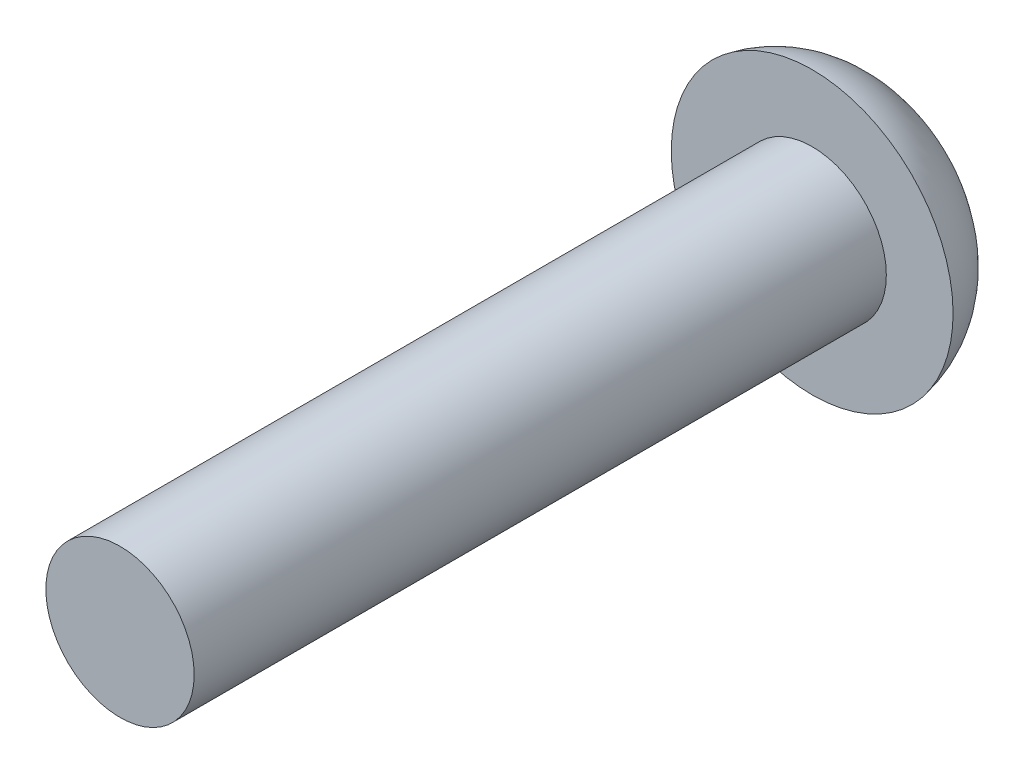
SolidWorks part; units mm, degrees
ref_plane "前视基准面" through (0, 0, 0) normal (0, 0, 1) x (1, 0, 0)
ref_plane "上视基准面" through (0, 0, 0) normal (0, 1, 0) x (1, 0, 0)
ref_plane "右视基准面" through (0, 0, 0) normal (1, 0, 0) x (0, 0, -1)
sketch "草图1" plane through (0, 0, 0) normal (0, 0, 1) x (1, 0, 0)
  circle A0 centre (0, 0) radius 1.5
extrude "凸台-拉伸1" add sketch "草图1" along normal blind 14
sketch "草图2" plane through (0, 0, 0) normal (0, 0, -1) x (-1, 0, 0)
  circle A0 centre (0, 0) radius 2.85
extrude "凸台-拉伸2" add sketch "草图2" along normal blind 1.65
fillet "圆角1" radius 2 1 edges at (-2.85, 0, -1.65)
sketch "草图3" plane through (0, 0, -1.65) normal (0, 0, -1) x (-1, 0, 0)
  line L0 (0, 2.85) -> (0, -2.85) construction
  line L1 (-2.85, 0) -> (2.85, 0) construction
  line L2 (-2.85, 0.25) -> (2.85, 0.25) construction
  line L3 (0.25, 2.85) -> (0.25, -2.85) construction
  line L4 (-2.85, -0.25) -> (2.85, -0.25) construction
  line L5 (-0.25, 2.85) -> (-0.25, -2.85) construction
  line L7 (2.85, 0.25) -> (2.85, -0.25)
  line L8 (-0.25, 2.85) -> (0.25, 2.85)
  line L10 (-0.25, 2.85) -> (-0.25, 0.25)
  line L11 (0.25, 2.85) -> (0.25, 0.25)
  line L12 (2.85, 0.25) -> (0.25, 0.25)
  line L13 (2.85, -0.25) -> (0.25, -0.25)
  line L15 (0.25, -2.85) -> (0.25, -0.25)
  line L16 (-0.25, -2.85) -> (-0.25, -0.25)
  line L17 (0.25, -2.85) -> (-0.25, -2.85)
  line L18 (-2.85, -0.25) -> (-0.25, -0.25)
  line L19 (-2.85, 0.25) -> (-0.25, 0.25)
  line L20 (-2.85, -0.25) -> (-2.85, 0.25)
  line L21 (2.85, 0.25) -> (2.85, -0.25) [skipped]
  circle A1 centre (0, 0) radius 2.85 construction
  dimension "D1" = 0.25
  dimension "D2" = 0.25
  dimension "D3" = 4
extrude "切除-拉伸1" cut sketch "草图3" against normal blind 0.5
